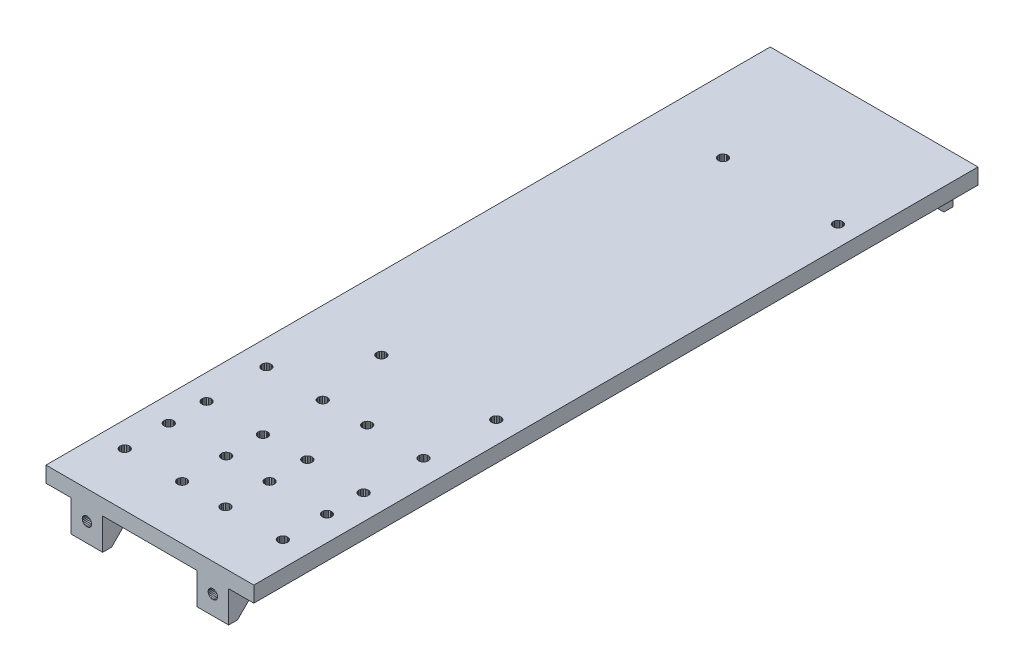
SolidWorks part; units mm, degrees
ref_plane "Front Plane" through (0, 0, 0) normal (0, 0, 1) x (1, 0, 0)
ref_plane "Top Plane" through (0, 0, 0) normal (0, 1, 0) x (1, 0, 0)
ref_plane "Right Plane" through (0, 0, 0) normal (1, 0, 0) x (0, 0, -1)
sketch "Sketch1" plane through (0, 0, 0) normal (0, 1, 0) x (1, 0, 0)
  line L0 (-33, -5) -> (-33, -235)
  line L1 (-33, -235) -> (33, -235)
  line L2 (33, -235) -> (33, -5)
  line L3 (33, -5) -> (-33, -5)
extrude "Boss-Extrude1" add sketch "Sketch1" against normal blind 5
sketch "Sketch2" plane through (0, -5, 0) normal (0, -1, 0) x (1, 0, 0)
  line L0 (-8.4326, 192.1754) -> (-8.3815, 191.7872)
  line L1 (-8.3815, 191.7872) -> (-8.2316, 191.4254)
  line L2 (-8.2316, 191.4254) -> (-7.9933, 191.1148)
  line L3 (-7.9933, 191.1148) -> (-7.6826, 190.8764)
  line L4 (-7.6826, 190.8764) -> (-7.3208, 190.7265)
  line L5 (-7.3208, 190.7265) -> (-6.9326, 190.6754)
  line L6 (-6.9326, 190.6754) -> (-6.5444, 190.7265)
  line L7 (-6.5444, 190.7265) -> (-6.1826, 190.8764)
  line L8 (-6.1826, 190.8764) -> (-5.8719, 191.1148)
  line L9 (-5.8719, 191.1148) -> (-5.6336, 191.4254)
  line L10 (-5.6336, 191.4254) -> (-5.4837, 191.7872)
  line L11 (-5.4837, 191.7872) -> (-5.4326, 192.1754)
  line L12 (-5.4326, 192.1754) -> (-5.4837, 192.5636)
  line L13 (-5.4837, 192.5636) -> (-5.6336, 192.9254)
  line L14 (-5.6336, 192.9254) -> (-5.8719, 193.2361)
  line L15 (-5.8719, 193.2361) -> (-6.1826, 193.4745)
  line L16 (-6.1826, 193.4745) -> (-6.5444, 193.6243)
  line L17 (-6.5444, 193.6243) -> (-6.9326, 193.6754)
  line L18 (-6.9326, 193.6754) -> (-7.3208, 193.6243)
  line L19 (-7.3208, 193.6243) -> (-7.6826, 193.4745)
  line L20 (-7.6826, 193.4745) -> (-7.9933, 193.2361)
  line L21 (-7.9933, 193.2361) -> (-8.2316, 192.9254)
  line L22 (-8.2316, 192.9254) -> (-8.3815, 192.5636)
  line L23 (-8.3815, 192.5636) -> (-8.4326, 192.1754)
extrude "Cut-Extrude1" cut sketch "Sketch2" against normal through all
sketch "Sketch3" plane through (0, -5, 0) normal (0, -1, 0) x (1, 0, 0)
  line L0 (-8.3735, 203.9015) -> (-8.3224, 203.5133)
  line L1 (-8.3224, 203.5133) -> (-8.1725, 203.1515)
  line L2 (-8.1725, 203.1515) -> (-7.9342, 202.8408)
  line L3 (-7.9342, 202.8408) -> (-7.6235, 202.6024)
  line L4 (-7.6235, 202.6024) -> (-7.2617, 202.4526)
  line L5 (-7.2617, 202.4526) -> (-6.8735, 202.4015)
  line L6 (-6.8735, 202.4015) -> (-6.4853, 202.4526)
  line L7 (-6.4853, 202.4526) -> (-6.1235, 202.6024)
  line L8 (-6.1235, 202.6024) -> (-5.8128, 202.8408)
  line L9 (-5.8128, 202.8408) -> (-5.5745, 203.1515)
  line L10 (-5.5745, 203.1515) -> (-5.4246, 203.5133)
  line L11 (-5.4246, 203.5133) -> (-5.3735, 203.9015)
  line L12 (-5.3735, 203.9015) -> (-5.4246, 204.2897)
  line L13 (-5.4246, 204.2897) -> (-5.5745, 204.6515)
  line L14 (-5.5745, 204.6515) -> (-5.8128, 204.9621)
  line L15 (-5.8128, 204.9621) -> (-6.1235, 205.2005)
  line L16 (-6.1235, 205.2005) -> (-6.4853, 205.3504)
  line L17 (-6.4853, 205.3504) -> (-6.8735, 205.4015)
  line L18 (-6.8735, 205.4015) -> (-7.2617, 205.3504)
  line L19 (-7.2617, 205.3504) -> (-7.6235, 205.2005)
  line L20 (-7.6235, 205.2005) -> (-7.9342, 204.9621)
  line L21 (-7.9342, 204.9621) -> (-8.1725, 204.6515)
  line L22 (-8.1725, 204.6515) -> (-8.3224, 204.2897)
  line L23 (-8.3224, 204.2897) -> (-8.3735, 203.9015)
extrude "Cut-Extrude2" cut sketch "Sketch3" against normal through all
sketch "Sketch4" plane through (0, -5, 0) normal (0, -1, 0) x (1, 0, 0)
  line L0 (-26.4489, 191.6118) -> (-26.299, 191.25)
  line L1 (-26.299, 191.25) -> (-26.0607, 190.9394)
  line L2 (-26.0607, 190.9394) -> (-25.75, 190.701)
  line L3 (-25.75, 190.701) -> (-25.3882, 190.5511)
  line L4 (-25.3882, 190.5511) -> (-25, 190.5)
  line L5 (-25, 190.5) -> (-24.6118, 190.5511)
  line L6 (-24.6118, 190.5511) -> (-24.25, 190.701)
  line L7 (-24.25, 190.701) -> (-23.9393, 190.9394)
  line L8 (-23.9393, 190.9394) -> (-23.701, 191.25)
  line L9 (-23.701, 191.25) -> (-23.5511, 191.6118)
  line L10 (-23.5511, 191.6118) -> (-23.5, 192)
  line L11 (-23.5, 192) -> (-23.5511, 192.3882)
  line L12 (-23.5511, 192.3882) -> (-23.701, 192.75)
  line L13 (-23.701, 192.75) -> (-23.9393, 193.0607)
  line L14 (-23.9393, 193.0607) -> (-24.25, 193.299)
  line L15 (-24.25, 193.299) -> (-24.6118, 193.4489)
  line L16 (-24.6118, 193.4489) -> (-25, 193.5)
  line L17 (-25, 193.5) -> (-25.3882, 193.4489)
  line L18 (-25.3882, 193.4489) -> (-25.75, 193.299)
  line L19 (-25.75, 193.299) -> (-26.0607, 193.0607)
  line L20 (-26.0607, 193.0607) -> (-26.299, 192.75)
  line L21 (-26.299, 192.75) -> (-26.4489, 192.3882)
  line L22 (-26.4489, 192.3882) -> (-26.5, 192)
  line L23 (-26.5, 192) -> (-26.4489, 191.6118)
extrude "Cut-Extrude3" cut sketch "Sketch4" against normal through all
sketch "Sketch5" plane through (0, -5, 0) normal (0, -1, 0) x (1, 0, 0)
  line L0 (-24.6118, 205.4489) -> (-25, 205.5)
  line L1 (-25, 205.5) -> (-25.3882, 205.4489)
  line L2 (-25.3882, 205.4489) -> (-25.75, 205.299)
  line L3 (-25.75, 205.299) -> (-26.0607, 205.0607)
  line L4 (-26.0607, 205.0607) -> (-26.299, 204.75)
  line L5 (-26.299, 204.75) -> (-26.4489, 204.3882)
  line L6 (-26.4489, 204.3882) -> (-26.5, 204)
  line L7 (-26.5, 204) -> (-26.4489, 203.6118)
  line L8 (-26.4489, 203.6118) -> (-26.299, 203.25)
  line L9 (-26.299, 203.25) -> (-26.0607, 202.9393)
  line L10 (-26.0607, 202.9393) -> (-25.75, 202.701)
  line L11 (-25.75, 202.701) -> (-25.3882, 202.5511)
  line L12 (-25.3882, 202.5511) -> (-25, 202.5)
  line L13 (-25, 202.5) -> (-24.6118, 202.5511)
  line L14 (-24.6118, 202.5511) -> (-24.25, 202.701)
  line L15 (-24.25, 202.701) -> (-23.9393, 202.9393)
  line L16 (-23.9393, 202.9393) -> (-23.701, 203.25)
  line L17 (-23.701, 203.25) -> (-23.5511, 203.6118)
  line L18 (-23.5511, 203.6118) -> (-23.5, 204)
  line L19 (-23.5, 204) -> (-23.5511, 204.3882)
  line L20 (-23.5511, 204.3882) -> (-23.701, 204.75)
  line L21 (-23.701, 204.75) -> (-23.9393, 205.0607)
  line L22 (-23.9393, 205.0607) -> (-24.25, 205.299)
  line L23 (-24.25, 205.299) -> (-24.6118, 205.4489)
extrude "Cut-Extrude4" cut sketch "Sketch5" against normal through all
sketch "Sketch6" plane through (0, -5, 0) normal (0, -1, 0) x (1, 0, 0)
  line L0 (-7.9342, 216.8408) -> (-7.6235, 216.6024)
  line L1 (-7.6235, 216.6024) -> (-7.2617, 216.4526)
  line L2 (-7.2617, 216.4526) -> (-6.8735, 216.4015)
  line L3 (-6.8735, 216.4015) -> (-6.4853, 216.4526)
  line L4 (-6.4853, 216.4526) -> (-6.1235, 216.6024)
  line L5 (-6.1235, 216.6024) -> (-5.8128, 216.8408)
  line L6 (-5.8128, 216.8408) -> (-5.5745, 217.1515)
  line L7 (-5.5745, 217.1515) -> (-5.4246, 217.5133)
  line L8 (-5.4246, 217.5133) -> (-5.3735, 217.9015)
  line L9 (-5.3735, 217.9015) -> (-5.4246, 218.2897)
  line L10 (-5.4246, 218.2897) -> (-5.5745, 218.6515)
  line L11 (-5.5745, 218.6515) -> (-5.8128, 218.9621)
  line L12 (-5.8128, 218.9621) -> (-6.1235, 219.2005)
  line L13 (-6.1235, 219.2005) -> (-6.4853, 219.3504)
  line L14 (-6.4853, 219.3504) -> (-6.8735, 219.4015)
  line L15 (-6.8735, 219.4015) -> (-7.2617, 219.3504)
  line L16 (-7.2617, 219.3504) -> (-7.6235, 219.2005)
  line L17 (-7.6235, 219.2005) -> (-7.9342, 218.9621)
  line L18 (-7.9342, 218.9621) -> (-8.1725, 218.6515)
  line L19 (-8.1725, 218.6515) -> (-8.3224, 218.2897)
  line L20 (-8.3224, 218.2897) -> (-8.3735, 217.9015)
  line L21 (-8.3735, 217.9015) -> (-8.3224, 217.5133)
  line L22 (-8.3224, 217.5133) -> (-8.1725, 217.1515)
  line L23 (-8.1725, 217.1515) -> (-7.9342, 216.8408)
extrude "Cut-Extrude5" cut sketch "Sketch6" against normal through all
sketch "Sketch7" plane through (0, -5, 0) normal (0, -1, 0) x (1, 0, 0)
  line L0 (-8.3815, 172.7872) -> (-8.2316, 172.4254)
  line L1 (-8.2316, 172.4254) -> (-7.9933, 172.1147)
  line L2 (-7.9933, 172.1147) -> (-7.6826, 171.8764)
  line L3 (-7.6826, 171.8764) -> (-7.3208, 171.7265)
  line L4 (-7.3208, 171.7265) -> (-6.9326, 171.6754)
  line L5 (-6.9326, 171.6754) -> (-6.5444, 171.7265)
  line L6 (-6.5444, 171.7265) -> (-6.1826, 171.8764)
  line L7 (-6.1826, 171.8764) -> (-5.8719, 172.1147)
  line L8 (-5.8719, 172.1147) -> (-5.6336, 172.4254)
  line L9 (-5.6336, 172.4254) -> (-5.4837, 172.7872)
  line L10 (-5.4837, 172.7872) -> (-5.4326, 173.1754)
  line L11 (-5.4326, 173.1754) -> (-5.4837, 173.5636)
  line L12 (-5.4837, 173.5636) -> (-5.6336, 173.9254)
  line L13 (-5.6336, 173.9254) -> (-5.8719, 174.2361)
  line L14 (-5.8719, 174.2361) -> (-6.1826, 174.4745)
  line L15 (-6.1826, 174.4745) -> (-6.5444, 174.6243)
  line L16 (-6.5444, 174.6243) -> (-6.9326, 174.6754)
  line L17 (-6.9326, 174.6754) -> (-7.3208, 174.6243)
  line L18 (-7.3208, 174.6243) -> (-7.6826, 174.4745)
  line L19 (-7.6826, 174.4745) -> (-7.9933, 174.2361)
  line L20 (-7.9933, 174.2361) -> (-8.2316, 173.9254)
  line L21 (-8.2316, 173.9254) -> (-8.3815, 173.5636)
  line L22 (-8.3815, 173.5636) -> (-8.4326, 173.1754)
  line L23 (-8.4326, 173.1754) -> (-8.3815, 172.7872)
extrude "Cut-Extrude6" cut sketch "Sketch7" against normal through all
sketch "Sketch8" plane through (0, -5, 0) normal (0, -1, 0) x (1, 0, 0)
  line L0 (-24.25, 216.701) -> (-23.9393, 216.9393)
  line L1 (-23.9393, 216.9393) -> (-23.701, 217.25)
  line L2 (-23.701, 217.25) -> (-23.5511, 217.6118)
  line L3 (-23.5511, 217.6118) -> (-23.5, 218)
  line L4 (-23.5, 218) -> (-23.5511, 218.3882)
  line L5 (-23.5511, 218.3882) -> (-23.701, 218.75)
  line L6 (-23.701, 218.75) -> (-23.9393, 219.0607)
  line L7 (-23.9393, 219.0607) -> (-24.25, 219.299)
  line L8 (-24.25, 219.299) -> (-24.6118, 219.4489)
  line L9 (-24.6118, 219.4489) -> (-25, 219.5)
  line L10 (-25, 219.5) -> (-25.3882, 219.4489)
  line L11 (-25.3882, 219.4489) -> (-25.75, 219.299)
  line L12 (-25.75, 219.299) -> (-26.0607, 219.0607)
  line L13 (-26.0607, 219.0607) -> (-26.299, 218.75)
  line L14 (-26.299, 218.75) -> (-26.4489, 218.3882)
  line L15 (-26.4489, 218.3882) -> (-26.5, 218)
  line L16 (-26.5, 218) -> (-26.4489, 217.6118)
  line L17 (-26.4489, 217.6118) -> (-26.299, 217.25)
  line L18 (-26.299, 217.25) -> (-26.0607, 216.9393)
  line L19 (-26.0607, 216.9393) -> (-25.75, 216.701)
  line L20 (-25.75, 216.701) -> (-25.3882, 216.5511)
  line L21 (-25.3882, 216.5511) -> (-25, 216.5)
  line L22 (-25, 216.5) -> (-24.6118, 216.5511)
  line L23 (-24.6118, 216.5511) -> (-24.25, 216.701)
extrude "Cut-Extrude7" cut sketch "Sketch8" against normal through all
sketch "Sketch9" plane through (0, -5, 0) normal (0, -1, 0) x (1, 0, 0)
  line L0 (5.5511, 203.6118) -> (5.701, 203.25)
  line L1 (5.701, 203.25) -> (5.9393, 202.9393)
  line L2 (5.9393, 202.9393) -> (6.25, 202.701)
  line L3 (6.25, 202.701) -> (6.6118, 202.5511)
  line L4 (6.6118, 202.5511) -> (7, 202.5)
  line L5 (7, 202.5) -> (7.3882, 202.5511)
  line L6 (7.3882, 202.5511) -> (7.75, 202.701)
  line L7 (7.75, 202.701) -> (8.0607, 202.9393)
  line L8 (8.0607, 202.9393) -> (8.299, 203.25)
  line L9 (8.299, 203.25) -> (8.4489, 203.6118)
  line L10 (8.4489, 203.6118) -> (8.5, 204)
  line L11 (8.5, 204) -> (8.4489, 204.3882)
  line L12 (8.4489, 204.3882) -> (8.299, 204.75)
  line L13 (8.299, 204.75) -> (8.0607, 205.0607)
  line L14 (8.0607, 205.0607) -> (7.75, 205.299)
  line L15 (7.75, 205.299) -> (7.3882, 205.4489)
  line L16 (7.3882, 205.4489) -> (7, 205.5)
  line L17 (7, 205.5) -> (6.6118, 205.4489)
  line L18 (6.6118, 205.4489) -> (6.25, 205.299)
  line L19 (6.25, 205.299) -> (5.9393, 205.0607)
  line L20 (5.9393, 205.0607) -> (5.701, 204.75)
  line L21 (5.701, 204.75) -> (5.5511, 204.3882)
  line L22 (5.5511, 204.3882) -> (5.5, 204)
  line L23 (5.5, 204) -> (5.5511, 203.6118)
extrude "Cut-Extrude8" cut sketch "Sketch9" against normal through all
sketch "Sketch10" plane through (0, -5, 0) normal (0, -1, 0) x (1, 0, 0)
  line L0 (5.701, 172.25) -> (5.9393, 171.9393)
  line L1 (5.9393, 171.9393) -> (6.25, 171.701)
  line L2 (6.25, 171.701) -> (6.6118, 171.5511)
  line L3 (6.6118, 171.5511) -> (7, 171.5)
  line L4 (7, 171.5) -> (7.3882, 171.5511)
  line L5 (7.3882, 171.5511) -> (7.75, 171.701)
  line L6 (7.75, 171.701) -> (8.0607, 171.9393)
  line L7 (8.0607, 171.9393) -> (8.299, 172.25)
  line L8 (8.299, 172.25) -> (8.4489, 172.6118)
  line L9 (8.4489, 172.6118) -> (8.5, 173)
  line L10 (8.5, 173) -> (8.4489, 173.3882)
  line L11 (8.4489, 173.3882) -> (8.299, 173.75)
  line L12 (8.299, 173.75) -> (8.0607, 174.0607)
  line L13 (8.0607, 174.0607) -> (7.75, 174.299)
  line L14 (7.75, 174.299) -> (7.3882, 174.4489)
  line L15 (7.3882, 174.4489) -> (7, 174.5)
  line L16 (7, 174.5) -> (6.6118, 174.4489)
  line L17 (6.6118, 174.4489) -> (6.25, 174.299)
  line L18 (6.25, 174.299) -> (5.9393, 174.0607)
  line L19 (5.9393, 174.0607) -> (5.701, 173.75)
  line L20 (5.701, 173.75) -> (5.5511, 173.3882)
  line L21 (5.5511, 173.3882) -> (5.5, 173)
  line L22 (5.5, 173) -> (5.5511, 172.6118)
  line L23 (5.5511, 172.6118) -> (5.701, 172.25)
extrude "Cut-Extrude9" cut sketch "Sketch10" against normal through all
sketch "Sketch11" plane through (0, -5, 0) normal (0, -1, 0) x (1, 0, 0)
  line L0 (5.5511, 191.6118) -> (5.701, 191.25)
  line L1 (5.701, 191.25) -> (5.9393, 190.9394)
  line L2 (5.9393, 190.9394) -> (6.25, 190.701)
  line L3 (6.25, 190.701) -> (6.6118, 190.5511)
  line L4 (6.6118, 190.5511) -> (7, 190.5)
  line L5 (7, 190.5) -> (7.3882, 190.5511)
  line L6 (7.3882, 190.5511) -> (7.75, 190.701)
  line L7 (7.75, 190.701) -> (8.0607, 190.9394)
  line L8 (8.0607, 190.9394) -> (8.299, 191.25)
  line L9 (8.299, 191.25) -> (8.4489, 191.6118)
  line L10 (8.4489, 191.6118) -> (8.5, 192)
  line L11 (8.5, 192) -> (8.4489, 192.3882)
  line L12 (8.4489, 192.3882) -> (8.299, 192.75)
  line L13 (8.299, 192.75) -> (8.0607, 193.0607)
  line L14 (8.0607, 193.0607) -> (7.75, 193.299)
  line L15 (7.75, 193.299) -> (7.3882, 193.4489)
  line L16 (7.3882, 193.4489) -> (7, 193.5)
  line L17 (7, 193.5) -> (6.6118, 193.4489)
  line L18 (6.6118, 193.4489) -> (6.25, 193.299)
  line L19 (6.25, 193.299) -> (5.9393, 193.0607)
  line L20 (5.9393, 193.0607) -> (5.701, 192.75)
  line L21 (5.701, 192.75) -> (5.5511, 192.3882)
  line L22 (5.5511, 192.3882) -> (5.5, 192)
  line L23 (5.5, 192) -> (5.5511, 191.6118)
extrude "Cut-Extrude10" cut sketch "Sketch11" against normal through all
sketch "Sketch12" plane through (0, -5, 0) normal (0, -1, 0) x (1, 0, 0)
  line L0 (8.5, 218) -> (8.4489, 218.3882)
  line L1 (8.4489, 218.3882) -> (8.299, 218.75)
  line L2 (8.299, 218.75) -> (8.0607, 219.0607)
  line L3 (8.0607, 219.0607) -> (7.75, 219.299)
  line L4 (7.75, 219.299) -> (7.3882, 219.4489)
  line L5 (7.3882, 219.4489) -> (7, 219.5)
  line L6 (7, 219.5) -> (6.6118, 219.4489)
  line L7 (6.6118, 219.4489) -> (6.25, 219.299)
  line L8 (6.25, 219.299) -> (5.9393, 219.0607)
  line L9 (5.9393, 219.0607) -> (5.701, 218.75)
  line L10 (5.701, 218.75) -> (5.5511, 218.3882)
  line L11 (5.5511, 218.3882) -> (5.5, 218)
  line L12 (5.5, 218) -> (5.5511, 217.6118)
  line L13 (5.5511, 217.6118) -> (5.701, 217.25)
  line L14 (5.701, 217.25) -> (5.9393, 216.9393)
  line L15 (5.9393, 216.9393) -> (6.25, 216.701)
  line L16 (6.25, 216.701) -> (6.6118, 216.5511)
  line L17 (6.6118, 216.5511) -> (7, 216.5)
  line L18 (7, 216.5) -> (7.3882, 216.5511)
  line L19 (7.3882, 216.5511) -> (7.75, 216.701)
  line L20 (7.75, 216.701) -> (8.0607, 216.9393)
  line L21 (8.0607, 216.9393) -> (8.299, 217.25)
  line L22 (8.299, 217.25) -> (8.4489, 217.6118)
  line L23 (8.4489, 217.6118) -> (8.5, 218)
extrude "Cut-Extrude11" cut sketch "Sketch12" against normal through all
sketch "Sketch13" plane through (0, -5, 0) normal (0, -1, 0) x (1, 0, 0)
  line L0 (-23.5511, 173.3882) -> (-23.701, 173.75)
  line L1 (-23.701, 173.75) -> (-23.9393, 174.0607)
  line L2 (-23.9393, 174.0607) -> (-24.25, 174.299)
  line L3 (-24.25, 174.299) -> (-24.6118, 174.4489)
  line L4 (-24.6118, 174.4489) -> (-25, 174.5)
  line L5 (-25, 174.5) -> (-25.3882, 174.4489)
  line L6 (-25.3882, 174.4489) -> (-25.75, 174.299)
  line L7 (-25.75, 174.299) -> (-26.0607, 174.0607)
  line L8 (-26.0607, 174.0607) -> (-26.299, 173.75)
  line L9 (-26.299, 173.75) -> (-26.4489, 173.3882)
  line L10 (-26.4489, 173.3882) -> (-26.5, 173)
  line L11 (-26.5, 173) -> (-26.4489, 172.6118)
  line L12 (-26.4489, 172.6118) -> (-26.299, 172.25)
  line L13 (-26.299, 172.25) -> (-26.0607, 171.9393)
  line L14 (-26.0607, 171.9393) -> (-25.75, 171.701)
  line L15 (-25.75, 171.701) -> (-25.3882, 171.5511)
  line L16 (-25.3882, 171.5511) -> (-25, 171.5)
  line L17 (-25, 171.5) -> (-24.6118, 171.5511)
  line L18 (-24.6118, 171.5511) -> (-24.25, 171.701)
  line L19 (-24.25, 171.701) -> (-23.9393, 171.9393)
  line L20 (-23.9393, 171.9393) -> (-23.701, 172.25)
  line L21 (-23.701, 172.25) -> (-23.5511, 172.6118)
  line L22 (-23.5511, 172.6118) -> (-23.5, 173)
  line L23 (-23.5, 173) -> (-23.5511, 173.3882)
extrude "Cut-Extrude12" cut sketch "Sketch13" against normal through all
sketch "Sketch14" plane through (0, -5, 0) normal (0, -1, 0) x (1, 0, 0)
  line L0 (-11.5, 43) -> (-11.4489, 42.6118)
  line L1 (-11.4489, 42.6118) -> (-11.299, 42.25)
  line L2 (-11.299, 42.25) -> (-11.0607, 41.9393)
  line L3 (-11.0607, 41.9393) -> (-10.75, 41.701)
  line L4 (-10.75, 41.701) -> (-10.3882, 41.5511)
  line L5 (-10.3882, 41.5511) -> (-10, 41.5)
  line L6 (-10, 41.5) -> (-9.6118, 41.5511)
  line L7 (-9.6118, 41.5511) -> (-9.25, 41.701)
  line L8 (-9.25, 41.701) -> (-8.9393, 41.9393)
  line L9 (-8.9393, 41.9393) -> (-8.701, 42.25)
  line L10 (-8.701, 42.25) -> (-8.5511, 42.6118)
  line L11 (-8.5511, 42.6118) -> (-8.5, 43)
  line L12 (-8.5, 43) -> (-8.5511, 43.3882)
  line L13 (-8.5511, 43.3882) -> (-8.701, 43.75)
  line L14 (-8.701, 43.75) -> (-8.9393, 44.0607)
  line L15 (-8.9393, 44.0607) -> (-9.25, 44.299)
  line L16 (-9.25, 44.299) -> (-9.6118, 44.4489)
  line L17 (-9.6118, 44.4489) -> (-10, 44.5)
  line L18 (-10, 44.5) -> (-10.3882, 44.4489)
  line L19 (-10.3882, 44.4489) -> (-10.75, 44.299)
  line L20 (-10.75, 44.299) -> (-11.0607, 44.0607)
  line L21 (-11.0607, 44.0607) -> (-11.299, 43.75)
  line L22 (-11.299, 43.75) -> (-11.4489, 43.3882)
  line L23 (-11.4489, 43.3882) -> (-11.5, 43)
extrude "Cut-Extrude13" cut sketch "Sketch14" against normal through all
sketch "Sketch15" plane through (0, -5, 0) normal (0, -1, 0) x (1, 0, 0)
  line L0 (23.8275, 203.1515) -> (24.0658, 202.8408)
  line L1 (24.0658, 202.8408) -> (24.3765, 202.6024)
  line L2 (24.3765, 202.6024) -> (24.7383, 202.4526)
  line L3 (24.7383, 202.4526) -> (25.1265, 202.4015)
  line L4 (25.1265, 202.4015) -> (25.5147, 202.4526)
  line L5 (25.5147, 202.4526) -> (25.8765, 202.6024)
  line L6 (25.8765, 202.6024) -> (26.1872, 202.8408)
  line L7 (26.1872, 202.8408) -> (26.4255, 203.1515)
  line L8 (26.4255, 203.1515) -> (26.5754, 203.5133)
  line L9 (26.5754, 203.5133) -> (26.6265, 203.9015)
  line L10 (26.6265, 203.9015) -> (26.5754, 204.2897)
  line L11 (26.5754, 204.2897) -> (26.4255, 204.6515)
  line L12 (26.4255, 204.6515) -> (26.1872, 204.9621)
  line L13 (26.1872, 204.9621) -> (25.8765, 205.2005)
  line L14 (25.8765, 205.2005) -> (25.5147, 205.3504)
  line L15 (25.5147, 205.3504) -> (25.1265, 205.4015)
  line L16 (25.1265, 205.4015) -> (24.7383, 205.3504)
  line L17 (24.7383, 205.3504) -> (24.3765, 205.2005)
  line L18 (24.3765, 205.2005) -> (24.0658, 204.9621)
  line L19 (24.0658, 204.9621) -> (23.8275, 204.6515)
  line L20 (23.8275, 204.6515) -> (23.6776, 204.2897)
  line L21 (23.6776, 204.2897) -> (23.6265, 203.9015)
  line L22 (23.6265, 203.9015) -> (23.6776, 203.5133)
  line L23 (23.6776, 203.5133) -> (23.8275, 203.1515)
extrude "Cut-Extrude14" cut sketch "Sketch15" against normal through all
sketch "Sketch16" plane through (0, -5, 0) normal (0, -1, 0) x (1, 0, 0)
  line L0 (23.6776, 217.5133) -> (23.8275, 217.1515)
  line L1 (23.8275, 217.1515) -> (24.0658, 216.8408)
  line L2 (24.0658, 216.8408) -> (24.3765, 216.6024)
  line L3 (24.3765, 216.6024) -> (24.7383, 216.4526)
  line L4 (24.7383, 216.4526) -> (25.1265, 216.4015)
  line L5 (25.1265, 216.4015) -> (25.5147, 216.4526)
  line L6 (25.5147, 216.4526) -> (25.8765, 216.6024)
  line L7 (25.8765, 216.6024) -> (26.1872, 216.8408)
  line L8 (26.1872, 216.8408) -> (26.4255, 217.1515)
  line L9 (26.4255, 217.1515) -> (26.5754, 217.5133)
  line L10 (26.5754, 217.5133) -> (26.6265, 217.9015)
  line L11 (26.6265, 217.9015) -> (26.5754, 218.2897)
  line L12 (26.5754, 218.2897) -> (26.4255, 218.6515)
  line L13 (26.4255, 218.6515) -> (26.1872, 218.9621)
  line L14 (26.1872, 218.9621) -> (25.8765, 219.2005)
  line L15 (25.8765, 219.2005) -> (25.5147, 219.3504)
  line L16 (25.5147, 219.3504) -> (25.1265, 219.4015)
  line L17 (25.1265, 219.4015) -> (24.7383, 219.3504)
  line L18 (24.7383, 219.3504) -> (24.3765, 219.2005)
  line L19 (24.3765, 219.2005) -> (24.0658, 218.9621)
  line L20 (24.0658, 218.9621) -> (23.8275, 218.6515)
  line L21 (23.8275, 218.6515) -> (23.6776, 218.2897)
  line L22 (23.6776, 218.2897) -> (23.6265, 217.9015)
  line L23 (23.6265, 217.9015) -> (23.6776, 217.5133)
extrude "Cut-Extrude15" cut sketch "Sketch16" against normal through all
sketch "Sketch17" plane through (0, -5, 0) normal (0, -1, 0) x (1, 0, 0)
  line L0 (-8.5511, 151.8882) -> (-8.701, 152.25)
  line L1 (-8.701, 152.25) -> (-8.9393, 152.5607)
  line L2 (-8.9393, 152.5607) -> (-9.25, 152.799)
  line L3 (-9.25, 152.799) -> (-9.6118, 152.9489)
  line L4 (-9.6118, 152.9489) -> (-10, 153)
  line L5 (-10, 153) -> (-10.3882, 152.9489)
  line L6 (-10.3882, 152.9489) -> (-10.75, 152.799)
  line L7 (-10.75, 152.799) -> (-11.0607, 152.5607)
  line L8 (-11.0607, 152.5607) -> (-11.299, 152.25)
  line L9 (-11.299, 152.25) -> (-11.4489, 151.8882)
  line L10 (-11.4489, 151.8882) -> (-11.5, 151.5)
  line L11 (-11.5, 151.5) -> (-11.4489, 151.1118)
  line L12 (-11.4489, 151.1118) -> (-11.299, 150.75)
  line L13 (-11.299, 150.75) -> (-11.0607, 150.4394)
  line L14 (-11.0607, 150.4394) -> (-10.75, 150.201)
  line L15 (-10.75, 150.201) -> (-10.3882, 150.0511)
  line L16 (-10.3882, 150.0511) -> (-10, 150)
  line L17 (-10, 150) -> (-9.6118, 150.0511)
  line L18 (-9.6118, 150.0511) -> (-9.25, 150.201)
  line L19 (-9.25, 150.201) -> (-8.9393, 150.4394)
  line L20 (-8.9393, 150.4394) -> (-8.701, 150.75)
  line L21 (-8.701, 150.75) -> (-8.5511, 151.1118)
  line L22 (-8.5511, 151.1118) -> (-8.5, 151.5)
  line L23 (-8.5, 151.5) -> (-8.5511, 151.8882)
extrude "Cut-Extrude16" cut sketch "Sketch17" against normal through all
sketch "Sketch18" plane through (0, -5, 0) normal (0, -1, 0) x (1, 0, 0)
  line L0 (23.6185, 191.7872) -> (23.7684, 191.4254)
  line L1 (23.7684, 191.4254) -> (24.0067, 191.1148)
  line L2 (24.0067, 191.1148) -> (24.3174, 190.8764)
  line L3 (24.3174, 190.8764) -> (24.6792, 190.7265)
  line L4 (24.6792, 190.7265) -> (25.0674, 190.6754)
  line L5 (25.0674, 190.6754) -> (25.4556, 190.7265)
  line L6 (25.4556, 190.7265) -> (25.8174, 190.8764)
  line L7 (25.8174, 190.8764) -> (26.1281, 191.1148)
  line L8 (26.1281, 191.1148) -> (26.3664, 191.4254)
  line L9 (26.3664, 191.4254) -> (26.5163, 191.7872)
  line L10 (26.5163, 191.7872) -> (26.5674, 192.1754)
  line L11 (26.5674, 192.1754) -> (26.5163, 192.5636)
  line L12 (26.5163, 192.5636) -> (26.3664, 192.9254)
  line L13 (26.3664, 192.9254) -> (26.1281, 193.2361)
  line L14 (26.1281, 193.2361) -> (25.8174, 193.4745)
  line L15 (25.8174, 193.4745) -> (25.4556, 193.6243)
  line L16 (25.4556, 193.6243) -> (25.0674, 193.6754)
  line L17 (25.0674, 193.6754) -> (24.6792, 193.6243)
  line L18 (24.6792, 193.6243) -> (24.3174, 193.4745)
  line L19 (24.3174, 193.4745) -> (24.0067, 193.2361)
  line L20 (24.0067, 193.2361) -> (23.7684, 192.9254)
  line L21 (23.7684, 192.9254) -> (23.6185, 192.5636)
  line L22 (23.6185, 192.5636) -> (23.5674, 192.1754)
  line L23 (23.5674, 192.1754) -> (23.6185, 191.7872)
extrude "Cut-Extrude17" cut sketch "Sketch18" against normal through all
sketch "Sketch19" plane through (0, -5, 0) normal (0, -1, 0) x (1, 0, 0)
  line L0 (24.701, 150.25) -> (24.9393, 149.9393)
  line L1 (24.9393, 149.9393) -> (25.25, 149.701)
  line L2 (25.25, 149.701) -> (25.6118, 149.5511)
  line L3 (25.6118, 149.5511) -> (26, 149.5)
  line L4 (26, 149.5) -> (26.3882, 149.5511)
  line L5 (26.3882, 149.5511) -> (26.75, 149.701)
  line L6 (26.75, 149.701) -> (27.0607, 149.9393)
  line L7 (27.0607, 149.9393) -> (27.299, 150.25)
  line L8 (27.299, 150.25) -> (27.4489, 150.6118)
  line L9 (27.4489, 150.6118) -> (27.5, 151)
  line L10 (27.5, 151) -> (27.4489, 151.3882)
  line L11 (27.4489, 151.3882) -> (27.299, 151.75)
  line L12 (27.299, 151.75) -> (27.0607, 152.0607)
  line L13 (27.0607, 152.0607) -> (26.75, 152.299)
  line L14 (26.75, 152.299) -> (26.3882, 152.4489)
  line L15 (26.3882, 152.4489) -> (26, 152.5)
  line L16 (26, 152.5) -> (25.6118, 152.4489)
  line L17 (25.6118, 152.4489) -> (25.25, 152.299)
  line L18 (25.25, 152.299) -> (24.9393, 152.0607)
  line L19 (24.9393, 152.0607) -> (24.701, 151.75)
  line L20 (24.701, 151.75) -> (24.5511, 151.3882)
  line L21 (24.5511, 151.3882) -> (24.5, 151)
  line L22 (24.5, 151) -> (24.5511, 150.6118)
  line L23 (24.5511, 150.6118) -> (24.701, 150.25)
extrude "Cut-Extrude18" cut sketch "Sketch19" against normal through all
sketch "Sketch20" plane through (0, -5, 0) normal (0, -1, 0) x (1, 0, 0)
  line L0 (25, 43) -> (25.0511, 42.6118)
  line L1 (25.0511, 42.6118) -> (25.201, 42.25)
  line L2 (25.201, 42.25) -> (25.4393, 41.9393)
  line L3 (25.4393, 41.9393) -> (25.75, 41.701)
  line L4 (25.75, 41.701) -> (26.1118, 41.5511)
  line L5 (26.1118, 41.5511) -> (26.5, 41.5)
  line L6 (26.5, 41.5) -> (26.8882, 41.5511)
  line L7 (26.8882, 41.5511) -> (27.25, 41.701)
  line L8 (27.25, 41.701) -> (27.5607, 41.9393)
  line L9 (27.5607, 41.9393) -> (27.799, 42.25)
  line L10 (27.799, 42.25) -> (27.9489, 42.6118)
  line L11 (27.9489, 42.6118) -> (28, 43)
  line L12 (28, 43) -> (27.9489, 43.3882)
  line L13 (27.9489, 43.3882) -> (27.799, 43.75)
  line L14 (27.799, 43.75) -> (27.5607, 44.0607)
  line L15 (27.5607, 44.0607) -> (27.25, 44.299)
  line L16 (27.25, 44.299) -> (26.8882, 44.4489)
  line L17 (26.8882, 44.4489) -> (26.5, 44.5)
  line L18 (26.5, 44.5) -> (26.1118, 44.4489)
  line L19 (26.1118, 44.4489) -> (25.75, 44.299)
  line L20 (25.75, 44.299) -> (25.4393, 44.0607)
  line L21 (25.4393, 44.0607) -> (25.201, 43.75)
  line L22 (25.201, 43.75) -> (25.0511, 43.3882)
  line L23 (25.0511, 43.3882) -> (25, 43)
extrude "Cut-Extrude19" cut sketch "Sketch20" against normal through all
sketch "Sketch21" plane through (0, -5, 0) normal (0, -1, 0) x (1, 0, 0)
  line L0 (-25, 225) -> (-25, 235)
  line L1 (-25, 235) -> (-15, 235)
  line L2 (-15, 235) -> (-15, 225)
  line L3 (-15, 225) -> (-25, 225)
extrude "Boss-Extrude2" add sketch "Sketch21" along normal blind 10
sketch "Sketch22" plane through (0, 0, 225) normal (0, 0, -1) x (-1, 0, 0)
  line L0 (18.9393, -7.9393) -> (18.701, -8.25)
  line L1 (18.701, -8.25) -> (18.5511, -8.6118)
  line L2 (18.5511, -8.6118) -> (18.5, -9)
  line L3 (18.5, -9) -> (18.5511, -9.3882)
  line L4 (18.5511, -9.3882) -> (18.701, -9.75)
  line L5 (18.701, -9.75) -> (18.9393, -10.0607)
  line L6 (18.9393, -10.0607) -> (19.25, -10.299)
  line L7 (19.25, -10.299) -> (19.6118, -10.4489)
  line L8 (19.6118, -10.4489) -> (20, -10.5)
  line L9 (20, -10.5) -> (20.3882, -10.4489)
  line L10 (20.3882, -10.4489) -> (20.75, -10.299)
  line L11 (20.75, -10.299) -> (21.0607, -10.0607)
  line L12 (21.0607, -10.0607) -> (21.299, -9.75)
  line L13 (21.299, -9.75) -> (21.4489, -9.3882)
  line L14 (21.4489, -9.3882) -> (21.5, -9)
  line L15 (21.5, -9) -> (21.4489, -8.6118)
  line L16 (21.4489, -8.6118) -> (21.299, -8.25)
  line L17 (21.299, -8.25) -> (21.0607, -7.9393)
  line L18 (21.0607, -7.9393) -> (20.75, -7.701)
  line L19 (20.75, -7.701) -> (20.3882, -7.5511)
  line L20 (20.3882, -7.5511) -> (20, -7.5)
  line L21 (20, -7.5) -> (19.6118, -7.5511)
  line L22 (19.6118, -7.5511) -> (19.25, -7.701)
  line L23 (19.25, -7.701) -> (18.9393, -7.9393)
extrude "Cut-Extrude20" cut sketch "Sketch22" against normal through all
sketch "Sketch23" plane through (0, -5, 0) normal (0, -1, 0) x (1, 0, 0)
  line L0 (-15, 15) -> (-15, 5)
  line L1 (-15, 5) -> (-25, 5)
  line L2 (-25, 5) -> (-25, 15)
  line L3 (-25, 15) -> (-15, 15)
extrude "Boss-Extrude3" add sketch "Sketch23" along normal blind 10
sketch "Sketch24" plane through (0, 0, 15) normal (0, 0, 1) x (1, 0, 0)
  line L0 (-18.5, -9) -> (-18.5511, -8.6118)
  line L1 (-18.5511, -8.6118) -> (-18.701, -8.25)
  line L2 (-18.701, -8.25) -> (-18.9393, -7.9393)
  line L3 (-18.9393, -7.9393) -> (-19.25, -7.701)
  line L4 (-19.25, -7.701) -> (-19.6118, -7.5511)
  line L5 (-19.6118, -7.5511) -> (-20, -7.5)
  line L6 (-20, -7.5) -> (-20.3882, -7.5511)
  line L7 (-20.3882, -7.5511) -> (-20.75, -7.701)
  line L8 (-20.75, -7.701) -> (-21.0607, -7.9393)
  line L9 (-21.0607, -7.9393) -> (-21.299, -8.25)
  line L10 (-21.299, -8.25) -> (-21.4489, -8.6118)
  line L11 (-21.4489, -8.6118) -> (-21.5, -9)
  line L12 (-21.5, -9) -> (-21.4489, -9.3882)
  line L13 (-21.4489, -9.3882) -> (-21.299, -9.75)
  line L14 (-21.299, -9.75) -> (-21.0607, -10.0607)
  line L15 (-21.0607, -10.0607) -> (-20.75, -10.299)
  line L16 (-20.75, -10.299) -> (-20.3882, -10.4489)
  line L17 (-20.3882, -10.4489) -> (-20, -10.5)
  line L18 (-20, -10.5) -> (-19.6118, -10.4489)
  line L19 (-19.6118, -10.4489) -> (-19.25, -10.299)
  line L20 (-19.25, -10.299) -> (-18.9393, -10.0607)
  line L21 (-18.9393, -10.0607) -> (-18.701, -9.75)
  line L22 (-18.701, -9.75) -> (-18.5511, -9.3882)
  line L23 (-18.5511, -9.3882) -> (-18.5, -9)
extrude "Cut-Extrude21" cut sketch "Sketch24" against normal through all
sketch "Sketch25" plane through (0, -5, 0) normal (0, -1, 0) x (1, 0, 0)
  line L0 (15, 225) -> (15, 235)
  line L1 (15, 235) -> (25, 235)
  line L2 (25, 235) -> (25, 225)
  line L3 (25, 225) -> (15, 225)
extrude "Boss-Extrude4" add sketch "Sketch25" along normal blind 10
sketch "Sketch26" plane through (0, 0, 225) normal (0, 0, -1) x (-1, 0, 0)
  line L0 (-20.75, -10.299) -> (-20.3882, -10.4489)
  line L1 (-20.3882, -10.4489) -> (-20, -10.5)
  line L2 (-20, -10.5) -> (-19.6118, -10.4489)
  line L3 (-19.6118, -10.4489) -> (-19.25, -10.299)
  line L4 (-19.25, -10.299) -> (-18.9393, -10.0607)
  line L5 (-18.9393, -10.0607) -> (-18.701, -9.75)
  line L6 (-18.701, -9.75) -> (-18.5511, -9.3882)
  line L7 (-18.5511, -9.3882) -> (-18.5, -9)
  line L8 (-18.5, -9) -> (-18.5511, -8.6118)
  line L9 (-18.5511, -8.6118) -> (-18.701, -8.25)
  line L10 (-18.701, -8.25) -> (-18.9393, -7.9393)
  line L11 (-18.9393, -7.9393) -> (-19.25, -7.701)
  line L12 (-19.25, -7.701) -> (-19.6118, -7.5511)
  line L13 (-19.6118, -7.5511) -> (-20, -7.5)
  line L14 (-20, -7.5) -> (-20.3882, -7.5511)
  line L15 (-20.3882, -7.5511) -> (-20.75, -7.701)
  line L16 (-20.75, -7.701) -> (-21.0607, -7.9393)
  line L17 (-21.0607, -7.9393) -> (-21.299, -8.25)
  line L18 (-21.299, -8.25) -> (-21.4489, -8.6118)
  line L19 (-21.4489, -8.6118) -> (-21.5, -9)
  line L20 (-21.5, -9) -> (-21.4489, -9.3882)
  line L21 (-21.4489, -9.3882) -> (-21.299, -9.75)
  line L22 (-21.299, -9.75) -> (-21.0607, -10.0607)
  line L23 (-21.0607, -10.0607) -> (-20.75, -10.299)
extrude "Cut-Extrude22" cut sketch "Sketch26" against normal through all
sketch "Sketch27" plane through (0, -5, 0) normal (0, -1, 0) x (1, 0, 0)
  line L0 (23.6185, 172.7872) -> (23.7684, 172.4254)
  line L1 (23.7684, 172.4254) -> (24.0067, 172.1148)
  line L2 (24.0067, 172.1148) -> (24.3174, 171.8764)
  line L3 (24.3174, 171.8764) -> (24.6792, 171.7265)
  line L4 (24.6792, 171.7265) -> (25.0674, 171.6754)
  line L5 (25.0674, 171.6754) -> (25.4556, 171.7265)
  line L6 (25.4556, 171.7265) -> (25.8174, 171.8764)
  line L7 (25.8174, 171.8764) -> (26.1281, 172.1148)
  line L8 (26.1281, 172.1148) -> (26.3664, 172.4254)
  line L9 (26.3664, 172.4254) -> (26.5163, 172.7872)
  line L10 (26.5163, 172.7872) -> (26.5674, 173.1754)
  line L11 (26.5674, 173.1754) -> (26.5163, 173.5636)
  line L12 (26.5163, 173.5636) -> (26.3664, 173.9254)
  line L13 (26.3664, 173.9254) -> (26.1281, 174.2361)
  line L14 (26.1281, 174.2361) -> (25.8174, 174.4745)
  line L15 (25.8174, 174.4745) -> (25.4556, 174.6243)
  line L16 (25.4556, 174.6243) -> (25.0674, 174.6754)
  line L17 (25.0674, 174.6754) -> (24.6792, 174.6243)
  line L18 (24.6792, 174.6243) -> (24.3174, 174.4745)
  line L19 (24.3174, 174.4745) -> (24.0067, 174.2361)
  line L20 (24.0067, 174.2361) -> (23.7684, 173.9254)
  line L21 (23.7684, 173.9254) -> (23.6185, 173.5636)
  line L22 (23.6185, 173.5636) -> (23.5674, 173.1754)
  line L23 (23.5674, 173.1754) -> (23.6185, 172.7872)
extrude "Cut-Extrude23" cut sketch "Sketch27" against normal through all
sketch "Sketch28" plane through (0, -5, 0) normal (0, -1, 0) x (1, 0, 0)
  line L0 (25, 15) -> (25, 5)
  line L1 (25, 5) -> (15, 5)
  line L2 (15, 5) -> (15, 15)
  line L3 (15, 15) -> (25, 15)
extrude "Boss-Extrude5" add sketch "Sketch28" along normal blind 10
sketch "Sketch29" plane through (0, 0, 5) normal (0, 0, -1) x (-1, 0, 0)
  line L0 (-20.75, -10.299) -> (-20.3882, -10.4489)
  line L1 (-20.3882, -10.4489) -> (-20, -10.5)
  line L2 (-20, -10.5) -> (-19.6118, -10.4489)
  line L3 (-19.6118, -10.4489) -> (-19.25, -10.299)
  line L4 (-19.25, -10.299) -> (-18.9393, -10.0607)
  line L5 (-18.9393, -10.0607) -> (-18.701, -9.75)
  line L6 (-18.701, -9.75) -> (-18.5511, -9.3882)
  line L7 (-18.5511, -9.3882) -> (-18.5, -9)
  line L8 (-18.5, -9) -> (-18.5511, -8.6118)
  line L9 (-18.5511, -8.6118) -> (-18.701, -8.25)
  line L10 (-18.701, -8.25) -> (-18.9393, -7.9393)
  line L11 (-18.9393, -7.9393) -> (-19.25, -7.701)
  line L12 (-19.25, -7.701) -> (-19.6118, -7.5511)
  line L13 (-19.6118, -7.5511) -> (-20, -7.5)
  line L14 (-20, -7.5) -> (-20.3882, -7.5511)
  line L15 (-20.3882, -7.5511) -> (-20.75, -7.701)
  line L16 (-20.75, -7.701) -> (-21.0607, -7.9393)
  line L17 (-21.0607, -7.9393) -> (-21.299, -8.25)
  line L18 (-21.299, -8.25) -> (-21.4489, -8.6118)
  line L19 (-21.4489, -8.6118) -> (-21.5, -9)
  line L20 (-21.5, -9) -> (-21.4489, -9.3882)
  line L21 (-21.4489, -9.3882) -> (-21.299, -9.75)
  line L22 (-21.299, -9.75) -> (-21.0607, -10.0607)
  line L23 (-21.0607, -10.0607) -> (-20.75, -10.299)
extrude "Cut-Extrude24" cut sketch "Sketch29" against normal up to next
sketch "Sketch30" plane through (25, 0, 0) normal (1, 0, 0) x (0, 0, -1)
  line L0 (-7.8284, -15) -> (-15, -15)
  line L1 (-15, -15) -> (-15, -7.8284)
  line L2 (-15, -7.8284) -> (-7.8284, -15)
extrude "Cut-Extrude25" cut sketch "Sketch30" against normal through all
sketch "Sketch31" plane through (25, 0, 0) normal (1, 0, 0) x (0, 0, -1)
  line L0 (-225, -7.8284) -> (-232.1716, -15)
  line L1 (-232.1716, -15) -> (-225, -15)
  line L2 (-225, -15) -> (-225, -7.8284)
extrude "Cut-Extrude26" cut sketch "Sketch31" against normal through all
